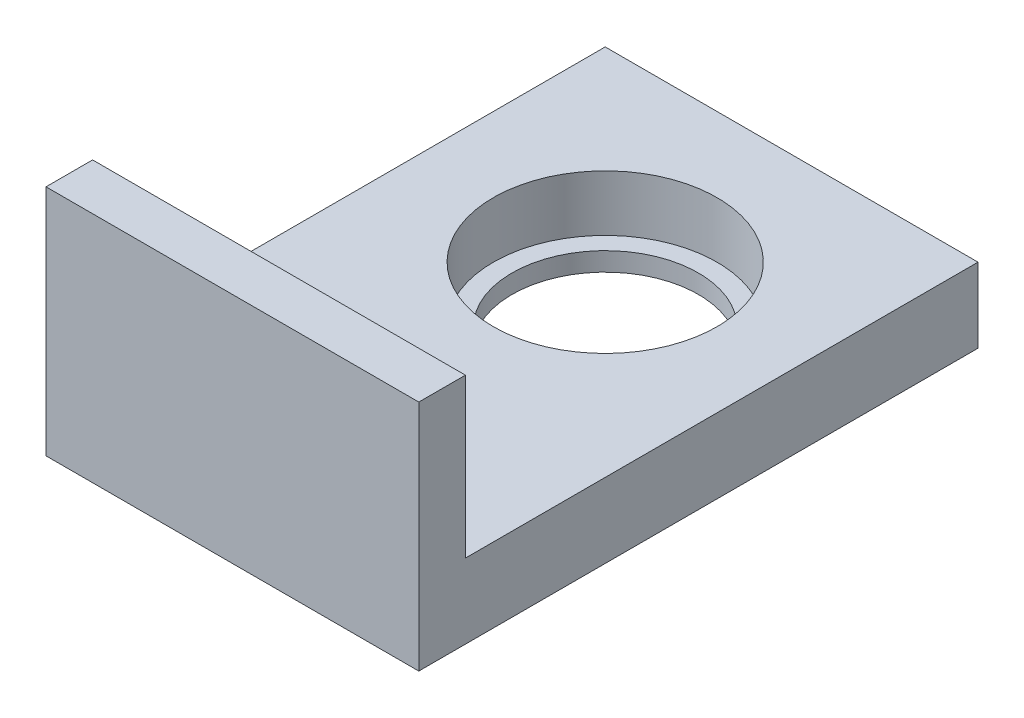
SolidWorks part; units mm, degrees
ref_plane "Front Plane" through (0, 0, 0) normal (0, 0, 1) x (1, 0, 0)
ref_plane "Top Plane" through (0, 0, 0) normal (0, 1, 0) x (1, 0, 0)
ref_plane "Right Plane" through (0, 0, 0) normal (1, 0, 0) x (0, 0, -1)
sketch "Sketch1" plane through (0, 0, 0) normal (0, 1, 0) x (1, 0, 0)
  line L1 (0, 0) -> (40, 0)
  line L2 (0, 0) -> (0, 55)
  line L3 (0, 55) -> (40, 55)
  line L4 (40, 0) -> (40, 55)
  line L5 (0, 0) -> (40, 0)
  line L6 (0, 0) -> (0, -5)
  line L7 (0, -5) -> (40, -5)
  line L8 (40, 0) -> (40, -5)
  dimension "D1" = 60
  dimension "D2" = 5
  dimension "D3" = 40
extrude "Boss-Extrude1" add sketch "Sketch1" along normal blind 8 contours L1 L4 L3 L2 region at (20, 0, -27.5)
extrude "Boss-Extrude2" add sketch "Sketch1<3>" along normal blind 25 contours L8 L1 L6 L7 region at (20, 0, 2.5)
sketch "Sketch1<3>" plane through (0, 0, 0) normal (0, 1, 0) x (1, 0, 0) same geometry as "Sketch1"
sketch "Sketch2" plane through (0, 8, 0) normal (0, 1, 0) x (1, 0, 0)
  line L1 (0, 0) -> (0, 55) construction
  line L2 (0, 0) -> (40, 0) construction
  circle A0 centre (20, 35) radius 12
  circle A5 centre (20, 35) radius 10
  dimension "D3" = 24
  dimension "D4" = 20
  dimension "D1" = 35
  dimension "D2" = 20
extrude "Cut-Extrude1" cut sketch "Sketch2" against normal blind 6 contours A0
extrude "Cut-Extrude2" cut sketch "Sketch2<3>" against normal blind 2 from offset 6 contours A5 offset against normal yes
sketch "Sketch2<3>" plane through (0, 8, 0) normal (0, 1, 0) x (1, 0, 0) same geometry as "Sketch2"
